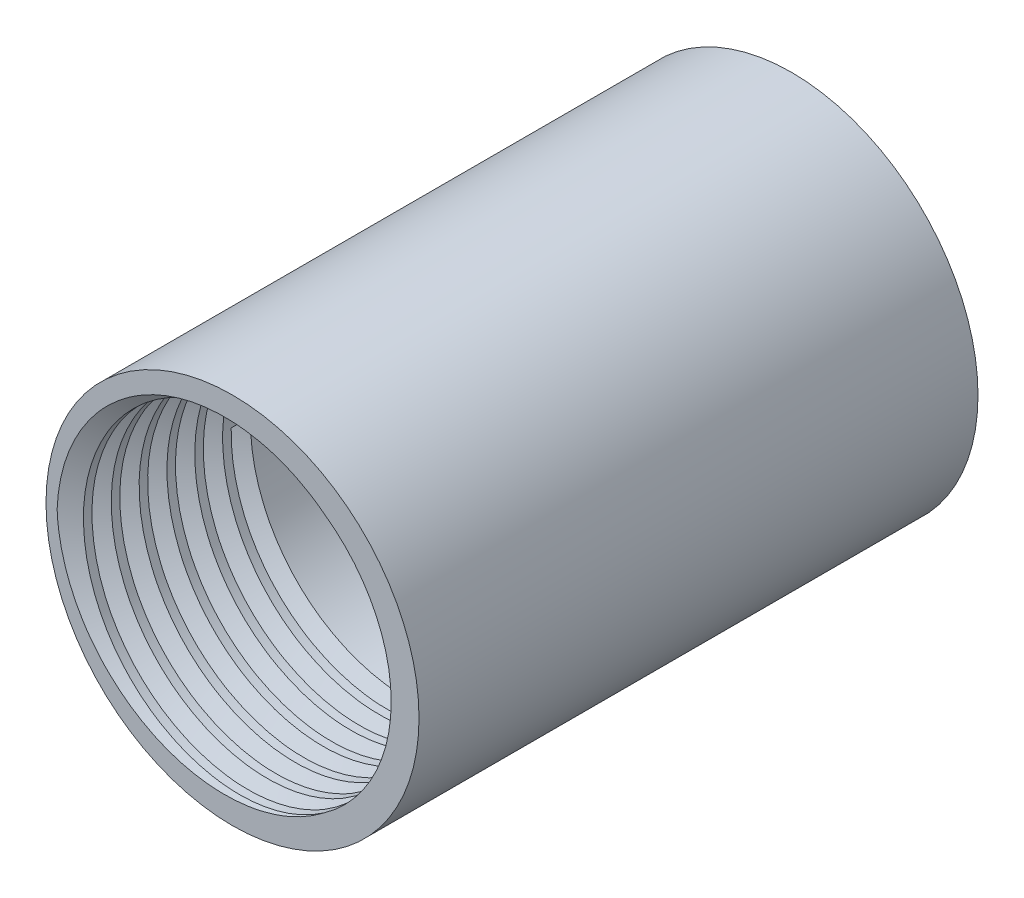
SolidWorks part; units mm, degrees
ref_plane "Plan de face" through (0, 0, 0) normal (0, 0, 1) x (1, 0, 0)
ref_plane "Plan de dessus" through (0, 0, 0) normal (0, 1, 0) x (1, 0, 0)
ref_plane "Plan de droite" through (0, 0, 0) normal (1, 0, 0) x (0, 0, -1)
sketch "Esquisse1" plane through (0, 0, 0) normal (0, 0, 1) x (1, 0, 0)
  circle A0 centre (0, 0) radius 3.35
extrude "Boss.-Extru.1" add sketch "Esquisse1" along normal blind 10.04
sketch "Esquisse2" plane through (0, 0, 10.04) normal (0, 0, 1) x (1, 0, 0)
  circle A0 centre (0, 0) radius 2.85
extrude "Enlèv. mat.-Extru.2" cut sketch "Esquisse2" against normal blind 9
sketch "Esquisse3" plane through (0, 0, 0) normal (0, 0, -1) x (-1, 0, 0)
  circle A0 centre (0, 0) radius 1.475
extrude "Enlèv. mat.-Extru.3" cut sketch "Esquisse3" against normal blind 9
sketch "Esquisse4" plane through (0, 0, 10.04) normal (0, 0, 1) x (1, 0, 0)
  circle A0 centre (0, 0) radius 2.85 construction
  circle A1 centre (0, 0) radius 2.85
curve "Hélice/Spirale1" pitch 0.5 height 3 radius 2.85 centre (0, 0, 10.04) axis (0, 0, -1) start towards (-1, 0, 0)
sketch "Esquisse5" plane through (0, 0, 0) normal (0, 1, 0) x (1, 0, 0)
  line L1 (-3.1503, -10.04) -> (-2.6998, -10.3001)
  line L2 (-2.6998, -10.3001) -> (-2.6998, -9.7799)
  line L3 (-2.6998, -9.7799) -> (-3.1503, -10.04)
  circle A0 centre (-2.85, -10.04) radius 0.1502 construction
sweep "Enlèvement de matière-Balayage2" cut profiles "Esquisse5" path "Hélice/Spirale1" align with end faces yes
